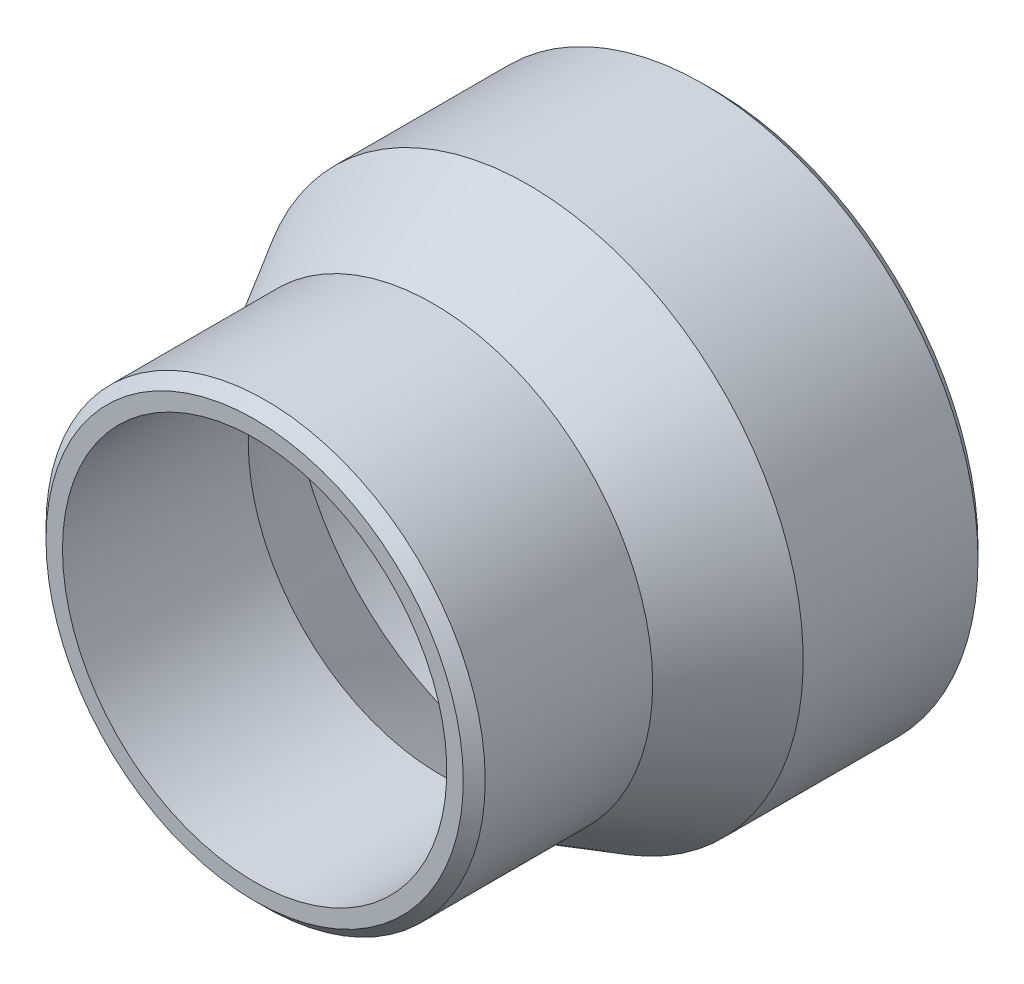
SolidWorks part; units mm, degrees
ref_plane "Pipe2 Plane" through (0, 0, 0) normal (0, 0, 1) x (1, 0, 0)
ref_plane "Top Plane" through (0, 0, 0) normal (0, 1, 0) x (1, 0, 0)
ref_plane "Right Plane" through (0, 0, 0) normal (1, 0, 0) x (0, 0, -1)
sketch "Sketch1" plane through (0, 0, 0) normal (1, 0, 0) x (0, 0, -1)
  line L0 (0, 0) -> (-106.3625, 0) construction
  line L1 (-106.3625, 0) -> (-106.3625, 50.8) construction
  line L2 (-106.3625, 50.8) -> (-65.0875, 50.8)
  line L3 (-65.0875, 50.8) -> (-42.9683, 63.5)
  line L4 (-42.9683, 63.5) -> (0, 63.5)
  line L5 (0, 63.5) -> (0, 0) construction
  line L6 (0, 63.5) -> (0, 57.15)
  line L7 (0, 57.15) -> (-41.275, 57.15)
  line L8 (-41.275, 57.15) -> (-63.3942, 44.45)
  line L9 (-63.3942, 44.45) -> (-106.3625, 44.45)
  line L10 (-106.3625, 44.45) -> (-106.3625, 50.8)
  line L11 (-65.0875, 50.8) -> (-65.0875, 0) construction
  line L12 (-41.275, 57.15) -> (-41.275, 0) construction
  line L13 (-65.0875, 25.4) -> (-41.275, 25.4) construction
  line L14 (-53.1812, 25.4) -> (-53.1812, 0) construction
  point P14 (-53.1812, 25.4)
  point P15 (-53.1812, 0)
  point P19 (0, 0)
  dimension "H" = 106.3625
  dimension "WallThickness" = 6.35
  dimension "PipeOD1" = 88.9
  dimension "D1" = 6.35
  dimension "N" = 23.8125
  dimension "PipeID2" = 114.3
revolve "Revolve1" add sketch "Sketch1" angle 360 about L0 region at (0, 53.975, 53.1812)
chamfer "Chamfer1" distance 2.54 angle 45 2 edges at (-63.5, 0, 0) (-50.8, 0, 106.3625)
ref_plane "Pipe1 Plane" through (0, 0, 106.3625) normal (0, 0, 1) x (1, 0, 0)
other "CPoint1" parameters "Diameter"=76.2, "StubLength"=76.2
ref_axis "Axis1" through (0, 0, 116.3625) along (0, 0, -1)
other "CPoint2" parameters "Diameter"=101.6, "StubLength"=114.3
ref_axis "Axis2" through (0, 0, -10) along (0, 0, 1)
other "RPoint1"
equation "\"D1@Sketch1\"=\"WallThickness@Sketch1\""
